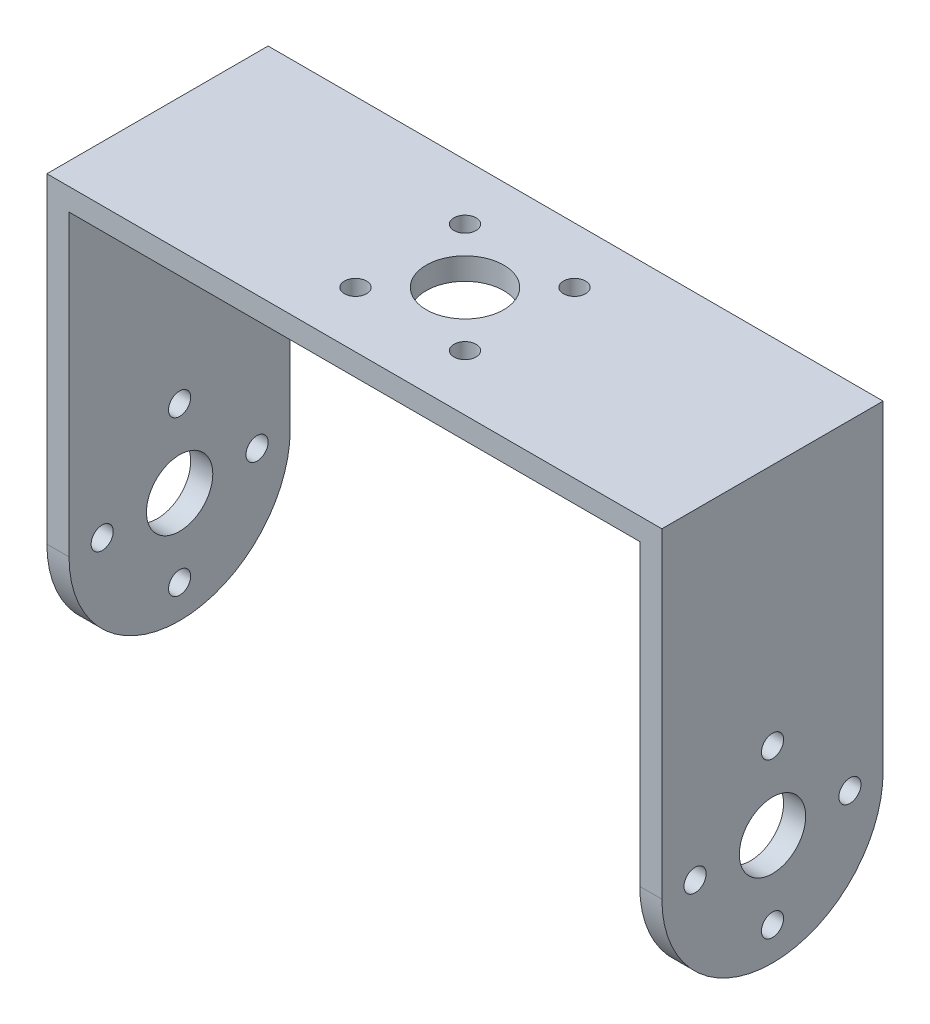
SolidWorks part; units mm, degrees
ref_plane "Front Plane" through (0, 0, 0) normal (0, 0, 1) x (1, 0, 0)
ref_plane "Top Plane" through (0, 0, 0) normal (0, 1, 0) x (1, 0, 0)
ref_plane "Right Plane" through (0, 0, 0) normal (1, 0, 0) x (0, 0, -1)
sketch "Sketch1" plane through (0, 0, 0) normal (0, 0, 1) x (1, 0, 0)
  line L0 (-25.8, -18.5) -> (-27.8, -18.5)
  line L1 (-25.8, 18.5) -> (25.8, 18.5)
  line L2 (-25.8, 18.5) -> (-25.8, -18.5)
  line L3 (-27.8, -18.5) -> (-27.8, 20.5)
  line L4 (25.8, 18.5) -> (25.8, -18.5)
  line L5 (-25.8, 18.5) -> (25.8, -18.5) construction
  line L6 (-25.8, -18.5) -> (25.8, 18.5) construction
  line L7 (-27.8, 20.5) -> (27.8, 20.5)
  line L8 (27.8, 20.5) -> (27.8, -18.5)
  line L9 (27.8, -18.5) -> (25.8, -18.5)
  point P0 (0, 0)
  dimension "D1" = 51.6
  dimension "D2" = 37
  dimension "D3" = 2
  dimension "D4" = 2
extrude "Boss-Extrude1" add sketch "Sketch1" along normal blind 20
fillet "Fillet1" radius 10 4 edges at (26.8, -18.5, 20) (26.8, -18.5, 0) (-26.8, -18.5, 20) (-26.8, -18.5, 0)
sketch "Sketch2" plane through (27.8, 0, 0) normal (1, 0, 0) x (0, 0, -1)
  line L0 (-10, -18.5) -> (-10, 20.5) construction
  line L1 (-20, 20.5) -> (0, 20.5) construction
  circle A0 centre (-10, -8.5) radius 3
  circle A1 centre (-10, -1.5) radius 1
  circle A2 centre (-3, -8.5) radius 1
  circle A3 centre (-10, -15.5) radius 1
  circle A4 centre (-17, -8.5) radius 1
  point P18 (-10, -8.5)
  dimension "D1" = 6
  dimension "D2" = 7
  dimension "D3" = 2
  dimension "D4" = 4
  dimension "D5" = 10
extrude "Cut-Extrude2" cut sketch "Sketch2" against normal blind 3.5 contours A1 L0 | L0 A1 | A4 | L0 A3 | A3 L0 | L0 A0 | A0 L0 | A2 region at (27.8, -15.5, 10.4244) region at (27.8, -1.5, 10.4244) region at (27.8, -1.5, 9.5756) region at (27.8, -8.5, 11.2732) region at (27.8, -8.5, 8.7268) region at (27.8, -15.5, 9.5756) region at (27.8, -8.5, 17)
pattern_linear "LPattern1" count 2 spacing 53.6 along (-1, 0, 0) of "Cut-Extrude2"
sketch "Sketch3" plane through (0, 20.5, 0) normal (0, 1, 0) x (1, 0, 0)
  line L0 (0, 0) -> (0, -20) construction
  line L1 (27.8, -20) -> (-27.8, -20) construction
  line L2 (4.9497, -5.0503) -> (0, -10) construction
  line L4 (-4.9497, -14.9497) -> (4.9497, -14.9497)
  line L5 (-4.9497, -14.9497) -> (-4.9497, -5.0503)
  line L6 (-4.9497, -5.0503) -> (4.9497, -5.0503)
  line L7 (4.9497, -14.9497) -> (4.9497, -5.0503)
  line L8 (-4.9497, -14.9497) -> (4.9497, -5.0503) construction
  line L9 (-4.9497, -5.0503) -> (4.9497, -14.9497) construction
  circle A0 centre (0, -10) radius 3.5
  circle A1 centre (4.9497, -5.0503) radius 1
  circle A2 centre (4.9497, -14.9497) radius 1
  circle A3 centre (-4.9497, -14.9497) radius 1
  circle A4 centre (-4.9497, -5.0503) radius 1
  point P21 (0, -10)
  dimension "D1" = 7
  dimension "D4" = 2
  dimension "D2" = 7
  dimension "D3" = 4
extrude "Cut-Extrude3" cut sketch "Sketch3" against normal up to next contours A0 | L7 A1 L6 | L6 A1 L7 | L5 A4 L6 | L6 A4 L5 | L5 A3 L4 | L4 A3 L5 | L4 A2 L7 | L7 A2 L4 region at (-4.5253, 20.5, 14.5253) region at (-5.0912, 20.5, 15.0912) region at (4.5253, 20.5, 14.5253) region at (5.0912, 20.5, 15.0912) region at (-5.0912, 20.5, 4.9088) region at (-4.5253, 20.5, 5.4747) region at (4.5253, 20.5, 5.4747) region at (5.0912, 20.5, 4.9088) region at (0, 20.5, 10)
